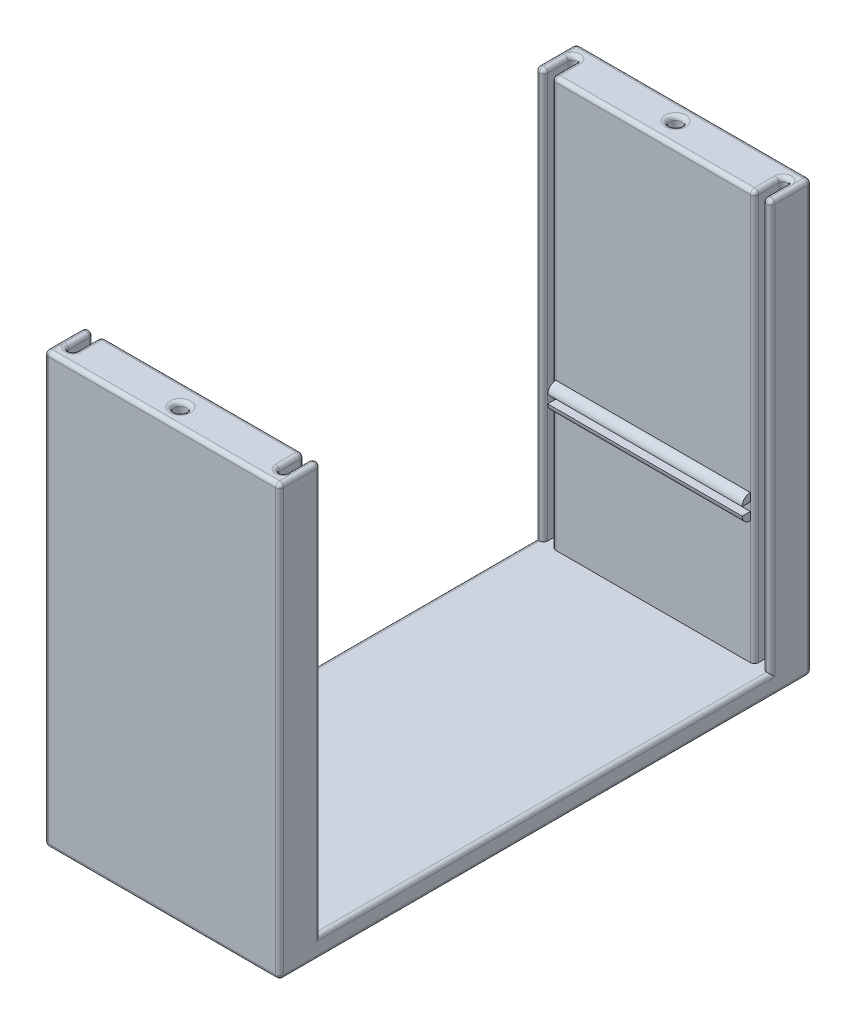
SolidWorks part; units mm, degrees
ref_plane "Front Plane" through (0, 0, 0) normal (0, 0, 1) x (1, 0, 0)
ref_plane "Top Plane" through (0, 0, 0) normal (0, 1, 0) x (1, 0, 0)
ref_plane "Right Plane" through (0, 0, 0) normal (1, 0, 0) x (0, 0, -1)
sketch "Sketch4" plane through (0, 0, 0) normal (0, 1, 0) x (1, 0, 0)
  line L0 (-28.75, 0) -> (28.75, 0) construction
  line L1 (-28.75, -65) -> (28.75, -65)
  line L2 (-28.75, -65) -> (-28.75, 65)
  line L3 (-28.75, 65) -> (28.75, 65)
  line L4 (28.75, -65) -> (28.75, 65)
  line L5 (-28.75, -65) -> (28.75, 65) construction
  line L6 (-28.75, 65) -> (28.75, -65) construction
  line L7 (0, -65) -> (0, 65) construction
  circle A0 centre (0, -60.5) radius 1.5
  circle A1 centre (0, 60.5) radius 1.5
  point P0 (0, 0)
  dimension "D3" = 3
  dimension "D4" = 3
  dimension "D5" = 0
  dimension "D1" = 130
  dimension "D2" = 57.5
extrude "Boss-Extrude3" add sketch "Sketch4" along normal blind 5
sketch "Sketch5" plane through (0, 5, 0) normal (0, 1, 0) x (1, 0, 0)
  line L0 (27.75, -55) -> (28.75, -55)
  line L5 (28.75, -65) -> (28.75, 65) construction
  line L10 (0, -65) -> (0, 65) construction
  line L11 (-28.75, -65) -> (28.75, -65)
  line L12 (28.75, 65) -> (-28.75, 65) construction
  line L30 (-28.75, -65) -> (-28.75, -55)
  line L31 (-28.75, -55) -> (-27.75, -55)
  line L32 (28.75, -65) -> (28.75, -55)
  line L33 (-28.75, 0) -> (28.75, 0) construction
  line L35 (26.75, -56) -> (26.75, -61)
  line L37 (24.75, -56) -> (24.75, -61)
  line L38 (-28.75, 65) -> (-28.75, -65) construction
  line L39 (-24.75, -56) -> (-24.75, -61)
  line L41 (-26.75, -56) -> (-26.75, -61)
  line L42 (-23.75, -55) -> (23.75, -55)
  line L43 (28.75, 65) -> (28.75, 55)
  line L44 (27.75, 55) -> (28.75, 55)
  line L45 (26.75, 56) -> (26.75, 61)
  line L47 (24.75, 56) -> (24.75, 61)
  line L48 (-23.75, 55) -> (23.75, 55)
  line L49 (-24.75, 56) -> (-24.75, 61)
  line L51 (-26.75, 56) -> (-26.75, 61)
  line L52 (-28.75, 55) -> (-27.75, 55)
  line L53 (-28.75, 65) -> (-28.75, 55)
  line L54 (-28.75, 65) -> (28.75, 65)
  arc A0 (27.75, -55) -> (26.75, -56) centre (27.75, -56) ccw
  arc A1 (23.75, -55) -> (24.75, -56) centre (23.75, -56) cw
  arc A4 (-23.75, -55) -> (-24.75, -56) centre (-23.75, -56) ccw
  arc A7 (-27.75, -55) -> (-26.75, -56) centre (-27.75, -56) cw
  arc A8 (27.75, 55) -> (26.75, 56) centre (27.75, 56) cw
  arc A11 (23.75, 55) -> (24.75, 56) centre (23.75, 56) ccw
  arc A12 (-23.75, 55) -> (-24.75, 56) centre (-23.75, 56) cw
  arc A15 (-27.75, 55) -> (-26.75, 56) centre (-27.75, 56) ccw
  circle A16 centre (0, -60.5) radius 1.5
  circle A17 centre (0, 60.5) radius 1.5
  arc A18 (24.75, -61) -> (26.75, -61) centre (25.75, -61) ccw
  arc A19 (-24.75, -61) -> (-26.75, -61) centre (-25.75, -61) cw
  arc A20 (-24.75, 61) -> (-26.75, 61) centre (-25.75, 61) ccw
  arc A21 (24.75, 61) -> (26.75, 61) centre (25.75, 61) cw
  point P12 (26.75, -55)
  dimension "D5" = 1
  dimension "D6" = 1
  dimension "D7" = 0
  dimension "D8" = 6
  dimension "D9" = 0
  dimension "D10" = 3
  dimension "D11" = 3
  dimension "D2" = 0
  dimension "D1" = 10
  dimension "D3" = 2
  dimension "D4" = 2
extrude "Boss-Extrude4" add sketch "Sketch5" along normal blind 100
fillet "Fillet2" radius 1 50 edges at (0, 0, -62) (0, 0, 62) (0, 105, 62) (-28.25, 105, 55) (-27.0429, 105, 55.2929) (-26.75, 105, 58.5) (-24.75, 105, 58.5) (-24.4571, 105, 55.2929) (0, 105, 55) (24.4571, 105, 55.2929) (24.75, 105, 58.5) (26.75, 105, 58.5) (27.0429, 105, 55.2929) (28.25, 105, 55) (0, 105, 65) (0, 0, 65) (-28.75, 55, -55) (-28.75, 5, 0) (-28.75, 55, 55) (-28.75, 105, 60) (-28.75, 52.5, 65) (-28.75, 0, 0) (0, 105, -62) (28.25, 105, -55) (27.0429, 105, -55.2929) (26.75, 105, -58.5) (24.75, 105, -58.5) (24.4571, 105, -55.2929) (0, 105, -55) (-24.4571, 105, -55.2929) (-24.75, 105, -58.5) (-26.75, 105, -58.5) (-27.0429, 105, -55.2929) (-28.25, 105, -55) (-28.75, 105, -60) (0, 105, -65) (-28.75, 52.5, -65) (0, 0, -65) (28.75, 52.5, 65) (28.75, 105, 60) (28.75, 55, 55) (28.75, 5, 0) (28.75, 55, -55) (28.75, 105, -60) (28.75, 52.5, -65) (28.75, 0, 0) (-25.75, 105, 62) (25.75, 105, 62) (25.75, 105, -62) (-25.75, 105, -62)
sketch "Sketch6" plane through (0, 0, 55) normal (0, 0, -1) x (-1, 0, 0)
  line L0 (-23.75, 104) -> (-23.75, 5) construction
  line L1 (-23.75, 35) -> (23.75, 35)
  line L2 (-23.75, 35) -> (-23.75, 37)
  line L3 (-23.75, 37) -> (23.75, 37)
  line L4 (23.75, 35) -> (23.75, 37)
  line L5 (23.75, 104) -> (23.75, 5) construction
  line L6 (-23.75, 5) -> (23.75, 5) construction
  dimension "D1" = 30
  dimension "D2" = 2
revolve "Revolve1" add sketch "Sketch6" angle 90 about L3 reverse direction yes
sketch "Sketch7" plane through (0, 0, 55) normal (0, 0, -1) x (-1, 0, 0)
  line L0 (-23.75, 104) -> (-23.75, 37) construction
  line L1 (-23.75, 41) -> (23.75, 41)
  line L2 (-23.75, 41) -> (-23.75, 39)
  line L3 (-23.75, 39) -> (23.75, 39)
  line L4 (23.75, 41) -> (23.75, 39)
  line L5 (23.75, 104) -> (23.75, 37) construction
  line L6 (-23.75, 5) -> (23.75, 5) construction
  dimension "D1" = 34
  dimension "D2" = 2
revolve "Revolve2" add sketch "Sketch7" angle 90 about L3
sketch "Sketch8" plane through (0, 0, -55) normal (0, 0, 1) x (1, 0, 0)
  line L0 (-23.75, 104) -> (-23.75, 5) construction
  line L1 (-23.75, 37) -> (23.75, 37)
  line L2 (-23.75, 37) -> (-23.75, 35)
  line L3 (-23.75, 35) -> (23.75, 35)
  line L4 (23.75, 37) -> (23.75, 35)
  line L5 (23.75, 104) -> (23.75, 5) construction
  line L6 (-23.75, 5) -> (23.75, 5) construction
  dimension "D1" = 30
  dimension "D2" = 2
revolve "Revolve3" add sketch "Sketch8" angle 90 about L1 reverse direction yes
sketch "Sketch9" plane through (0, 0, -55) normal (0, 0, 1) x (1, 0, 0)
  line L0 (-23.75, 104) -> (-23.75, 37) construction
  line L1 (-23.75, 41) -> (23.75, 41)
  line L2 (-23.75, 41) -> (-23.75, 39)
  line L3 (-23.75, 39) -> (23.75, 39)
  line L4 (23.75, 41) -> (23.75, 39)
  line L5 (23.75, 104) -> (23.75, 37) construction
  line L6 (-23.75, 5) -> (23.75, 5) construction
  dimension "D1" = 34
  dimension "D2" = 2
revolve "Revolve4" add sketch "Sketch9" angle 90 about L3
